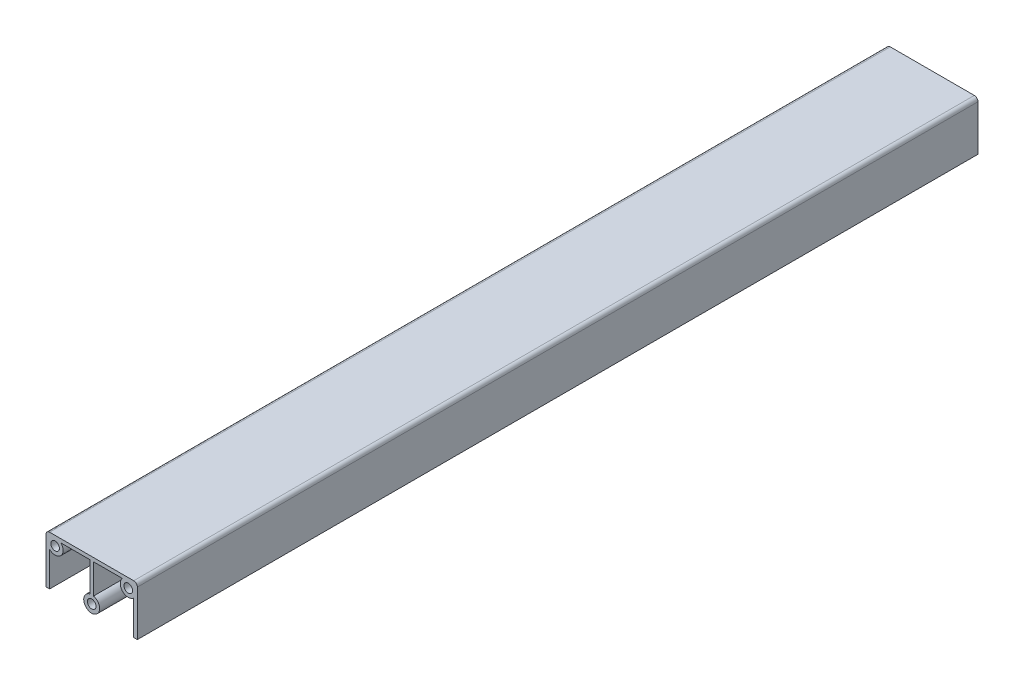
SolidWorks part; units mm, degrees
ref_plane "Front Plane" through (0, 0, 0) normal (0, 0, 1) x (1, 0, 0)
ref_plane "Top Plane" through (0, 0, 0) normal (0, 1, 0) x (1, 0, 0)
ref_plane "Right Plane" through (0, 0, 0) normal (1, 0, 0) x (0, 0, -1)
sketch "Sketch1" plane through (0, 0, 0) normal (0, 0, 1) x (1, 0, 0)
  line L0 (0, 31.75) -> (0, -31.75) construction
  line L1 (-31.75, -31.75) -> (31.75, -31.75)
  line L2 (-31.75, -31.75) -> (-31.75, 31.75)
  line L3 (-31.75, 31.75) -> (31.75, 31.75)
  line L4 (31.75, -31.75) -> (31.75, 31.75)
  line L5 (-31.75, -31.75) -> (31.75, 31.75) construction
  line L6 (-31.75, 31.75) -> (31.75, -31.75) construction
  line L7 (-31.75, 0) -> (31.75, 0) construction
  circle A0 centre (-25.4, 25.4) radius 3
  circle A1 centre (25.4, -25.4) radius 3
  circle A2 centre (-25.4, -25.4) radius 3
  circle A3 centre (25.4, 25.4) radius 3
  point P0 (0, 0)
  dimension "D3" = 6
  dimension "D9" = 50.8
  dimension "D4" = 50.8
  dimension "D1" = 63.5
  dimension "D2" = 63.5
  dimension "D5" = 6.35
extrude "Boss-Extrude1" add sketch "Sketch1" along normal mid plane 584.2
fillet "Fillet1" radius 2.54 4 edges at (-31.75, -31.75, 0) (31.75, -31.75, 0) (-31.75, 31.75, 0) (31.75, 31.75, 0)
sketch "Sketch7" plane through (0, 0, 292.1) normal (0, 0, 1) x (1, 0, 0)
  line L0 (0, 0) -> (0, -36.5826) construction
  line L1 (0, 0) -> (0, 40.0742) construction
  line L2 (29.21, 31.75) -> (-29.21, 31.75) construction
  line L3 (1.27, -2.2175) -> (1.27, -29.21)
  line L4 (1.27, 8.5675) -> (1.27, 29.21)
  line L5 (-1.27, -2.2175) -> (-1.27, -29.21)
  line L6 (-1.27, 8.5675) -> (-1.27, 29.21)
  line L7 (-1.27, 0) -> (-1.27, 40.0742) construction
  line L8 (1.27, 0) -> (1.27, 40.0742) construction
  line L9 (1.27, 0) -> (1.27, -36.5826) construction
  line L10 (-1.27, 0) -> (-1.27, -36.5826) construction
  line L11 (-1.27, 29.21) -> (-21.3781, 29.21)
  line L12 (1.27, -29.21) -> (21.3781, -29.21)
  line L13 (-29.21, 29.21) -> (-29.21, -29.21)
  line L14 (-29.21, -29.21) -> (29.21, -29.21)
  line L15 (29.21, -29.21) -> (29.21, 29.21)
  line L16 (29.21, 29.21) -> (-29.21, 29.21)
  line L17 (-29.21, 21.3781) -> (-29.21, -21.3781)
  line L18 (-21.3781, -29.21) -> (-1.27, -29.21)
  line L19 (29.21, -21.3781) -> (29.21, 21.3781)
  line L20 (21.3781, 29.21) -> (1.27, 29.21)
  arc A0 (1.27, 8.5675) -> (1.27, -2.2175) centre (0, 3.175) cw
  circle A1 centre (0, 3.175) radius 3
  arc A3 (-1.27, -2.2175) -> (-1.27, 8.5675) centre (0, 3.175) cw
  circle A4 centre (0, 3.175) radius 5.54 construction
  circle A5 centre (25.4, 25.4) radius 5.54
  arc A6 (21.3781, 29.21) -> (29.21, 21.3781) centre (25.4, 25.4) ccw
  circle A8 centre (-25.4, 25.4) radius 5.54
  arc A9 (-29.21, 21.3781) -> (-21.3781, 29.21) centre (-25.4, 25.4) ccw
  circle A10 centre (-25.4, -25.4) radius 5.54
  arc A11 (-21.3781, -29.21) -> (-29.21, -21.3781) centre (-25.4, -25.4) ccw
  circle A13 centre (25.4, -25.4) radius 5.54
  arc A14 (29.21, -21.3781) -> (21.3781, -29.21) centre (25.4, -25.4) ccw
  point P46 (5.54, 3.175)
  dimension "D6" = 28.575
  dimension "D10" = 22.225
  dimension "D1" = 2.54
  dimension "D2" = 2.54
  dimension "D3" = 2.54
  dimension "D4" = 2.54
  dimension "D5" = 2.54
  dimension "D7" = 2.54
  dimension "D8" = 1.27
  dimension "D9" = 1.27
extrude "Cut-Extrude3" cut sketch "Sketch7" against normal through all
sketch "Sketch3" plane through (0, 0, 292.1) normal (0, 0, 1) x (1, 0, 0)
  line L1 (-31.75, 29.21) -> (-31.75, -29.21) construction
  line L2 (-31.75, -2.4149) -> (31.9153, -2.4149)
  line L3 (-31.75, -2.4149) -> (-31.75, -31.8789)
  line L4 (-31.75, -31.8789) -> (31.9153, -31.8789)
  line L5 (31.9153, -2.4149) -> (31.9153, -31.8789)
  dimension "D1" = 29.464
extrude "Cut-Extrude2" cut sketch "Sketch3" against normal through all
